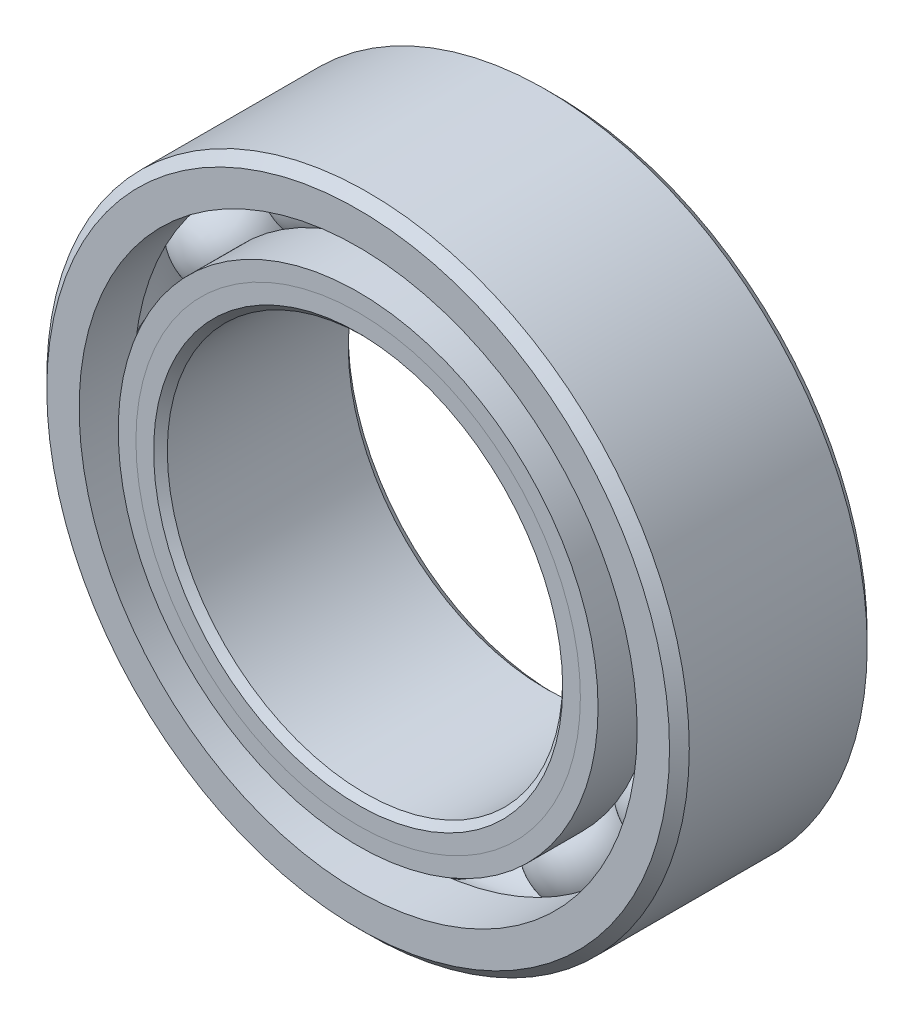
SolidWorks part; units mm, degrees
ref_plane "Front Plane" through (0, 0, 0) normal (0, 0, 1) x (1, 0, 0)
ref_plane "Top Plane" through (0, 0, 0) normal (0, 1, 0) x (1, 0, 0)
ref_plane "Right Plane" through (0, 0, 0) normal (1, 0, 0) x (0, 0, -1)
sketch "Sketch1" plane through (0, 0, 0) normal (1, 0, 0) x (0, 0, -1)
  line L0 (-6.35, 0) -> (6.35, 0) construction
  line L1 (0, 20.6375) -> (0, -20.6375) construction
  line L2 (5.715, 20.6375) -> (-5.715, 20.6375)
  line L3 (-5.715, 20.6375) -> (-6.35, 20.0025)
  line L4 (-6.35, 20.0025) -> (-6.35, 17.9248)
  line L5 (-6.35, 17.9248) -> (-2.8222, 17.9248)
  line L6 (6.35, 17.9248) -> (2.8222, 17.9248)
  line L7 (6.35, 20.0025) -> (6.35, 17.9248)
  line L8 (5.715, 20.6375) -> (6.35, 20.0025)
  line L9 (0, 20.6375) -> (0, 16.6687) construction
  line L10 (0, 16.6687) -> (0, 12.7) construction
  arc A0 (-2.8222, 17.9248) -> (2.8222, 17.9248) centre (0, 16.6687) cw
  point P14 (0, 12.7)
  dimension "Width" = 12.7
  dimension "OD" = 41.275
  dimension "D1" = 45
  dimension "D2" = 0.635
  dimension "D3" = 5.6444
  dimension "D4" = 1.256
revolve "Revolve1" add sketch "Sketch1" angle 360 about L0
sketch "Sketch2" plane through (0, 0, 0) normal (1, 0, 0) x (0, 0, -1)
  line L0 (-6.35, 15.4127) -> (-2.8222, 15.4127)
  line L1 (-6.35, 20.0025) -> (-6.35, -20.0025) construction
  line L2 (-6.35, 15.4127) -> (-6.35, 14.2763)
  line L3 (-6.35, 14.2763) -> (-5.2136, 13.1398)
  line L4 (-5.2136, 13.1398) -> (0, 13.1398)
  line L5 (0, 20.6375) -> (0, -20.6375) construction
  line L6 (0, 13.1398) -> (0, 13.5796)
  line L7 (0, 13.5796) -> (0, 12.7) construction
  line L8 (-6.35, 15.4127) -> (-6.35, 13.1398) construction
  line L9 (-6.35, 13.1398) -> (-5.2136, 13.1398) construction
  arc A0 (-2.8222, 15.4127) -> (0, 13.5796) centre (0, 16.6687) ccw
  arc A1 (2.8222, 17.9248) -> (-2.8222, 17.9248) centre (0, 16.6687) ccw construction
  circle A2 centre (0, 16.6687) radius 3.0891 construction
  dimension "D1" = 45
revolve "Revolve2" add sketch "Sketch2" angle 360 about L0
sketch "Sketch3" plane through (0, 0, 0) normal (1, 0, 0) x (0, 0, -1)
  line L0 (-6.35, 14.2763) -> (-5.2136, 13.1398)
  line L1 (-5.2136, 13.1398) -> (0, 13.1398)
  line L2 (0, 13.1398) -> (0, 13.5796)
  line L3 (-6.35, 14.2763) -> (-6.35, 13.1398)
  line L4 (-6.35, 15.4127) -> (-6.35, 13.1398) construction
  line L5 (-6.35, 13.1398) -> (-5.9102, 12.7)
  line L6 (-5.9102, 12.7) -> (5.715, 12.7)
  line L7 (5.715, 20.6375) -> (5.715, -20.6375) construction
  line L8 (5.715, 12.7) -> (6.35, 13.335)
  line L9 (6.35, -20.0025) -> (6.35, 20.0025) construction
  line L10 (6.35, 13.335) -> (6.35, 15.4127)
  line L11 (6.35, 15.4127) -> (2.8222, 15.4127)
  line L13 (5.715, 20.6375) -> (6.35, 20.0025) construction
  circle A0 centre (0, 16.6687) radius 3.0891 construction
  arc A1 (2.8222, 15.4127) -> (0, 13.5796) centre (0, 16.6687) cw
revolve "Revolve3" add sketch "Sketch3" angle 360 about L0
sketch "Sketch4" plane through (0, 0, 0) normal (1, 0, 0) x (0, 0, -1)
  line L0 (-3.0891, 16.6687) -> (3.0891, 16.6687)
  circle A1 centre (0, 16.6687) radius 3.0891 construction
  arc A2 (-3.0891, 16.6687) -> (3.0891, 16.6687) centre (0, 16.6687) cw
  arc A3 (2.8222, 17.9248) -> (-2.8222, 17.9248) centre (0, 16.6687) ccw construction
revolve "Revolve4" add sketch "Sketch4" angle 360 about L0
ref_axis "Axis1" through (0, 0, -6.35) along (0, 0, 1)
pattern_circular "CirPattern1" count 12 every 30 about axis through (0, 0, -6.35) along (0, 0, 1) of bodies 104
equation "\"D2@Sketch1\" = \"Width@Sketch1\"*.05"
equation "\"D3@Sketch1\" = \"Width@Sketch1\"/2.25"
equation "\"D4@Sketch1\" = (((\"OD@Sketch1\"-\"Width@Sketch1\")/2)/3.25)/3.5"
equation "\"D2@CirPattern1\" = 360/\"Balls@CirPattern1\""
